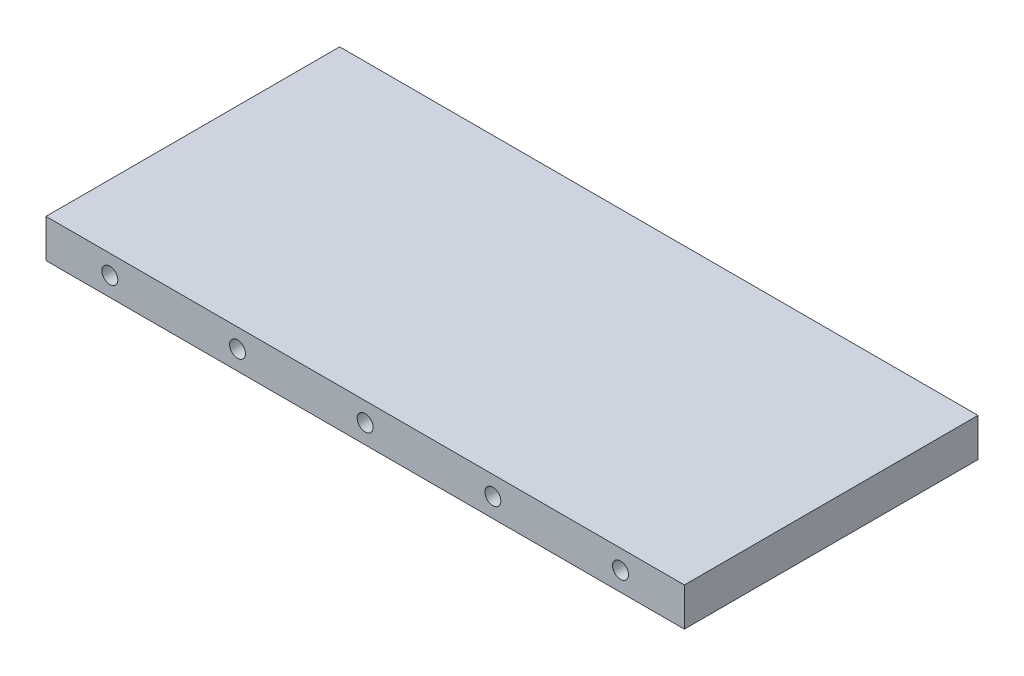
SolidWorks part; units mm, degrees
material "6061-T6 (SS)"
ref_plane "Front Plane" through (0, 0, 0) normal (0, 0, 1) x (1, 0, 0)
ref_plane "Top Plane" through (0, 0, 0) normal (0, 1, 0) x (1, 0, 0)
ref_plane "Right Plane" through (0, 0, 0) normal (1, 0, 0) x (0, 0, -1)
sketch "Sketch1" plane through (0, 0, 0) normal (0, 1, 0) x (1, 0, 0)
  line L1 (0, 0) -> (100, 0)
  line L2 (0, 0) -> (0, 46)
  line L3 (0, 46) -> (100, 46)
  line L4 (100, 0) -> (100, 46)
  dimension "D1" = 100
  dimension "D2" = 46
extrude "Boss-Extrude1" add sketch "Sketch1" along normal blind 6
sketch "Sketch5" plane through (0, 0, -46) normal (0, 0, -1) x (-1, 0, 0)
  line L1 (-100, 0) -> (0, 0) construction
  line L3 (-50, 3) -> (-50, 6) construction
  line L4 (-100, 6) -> (0, 6) construction
  point P0 (-90, 3)
  point P12 (-70, 3)
  point P13 (-50, 3)
  point P14 (-30, 3)
  point P15 (-10, 3)
  dimension "D1" = 3
  dimension "D2" = 5
  dimension "D3" = 20
hole_wizard "Tap Drill for M3 Tap1" positions "Sketch5" profile "Sketch7" hole size "M3" standard "DIN" end condition through all
sketch "Sketch7" plane through (90, 3, -46) normal (1, 0, 0) x (0, 1, 0)
  line L0 (0, 0) -> (0, 46)
  line L1 (0, 46) -> (1.25, 46)
  line L2 (1.25, 46) -> (1.25, 0)
  line L5 (1.25, 0) -> (0, 0)
  line L11 (0, -6.35) -> (0, 107.95) construction
  dimension "Thru Hole Dia." = 2.5
  dimension "Thru Hole Depth" = 46
